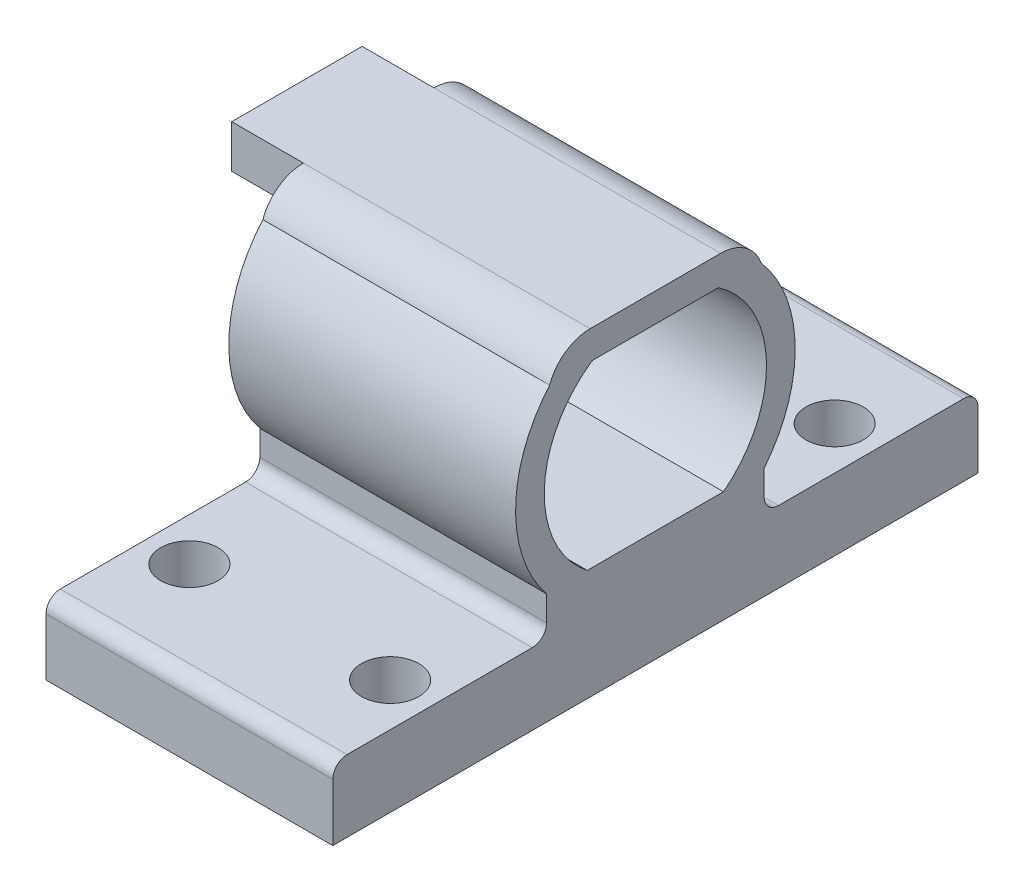
SolidWorks part; units mm, degrees
ref_plane "Front Plane" through (0, 0, 0) normal (0, 0, 1) x (1, 0, 0)
ref_plane "Top Plane" through (0, 0, 0) normal (0, 1, 0) x (1, 0, 0)
ref_plane "Right Plane" through (0, 0, 0) normal (1, 0, 0) x (0, 0, -1)
sketch "Sketch1" plane through (0, 0, 0) normal (0, 0, 1) x (1, 0, 0)
  line L1 (-5.0753, 3.8065) -> (14.9247, 3.8065)
  line L2 (-5.0753, 3.8065) -> (-5.0753, -0.9435)
  line L3 (-5.0753, -0.9435) -> (14.9247, -0.9435)
  line L4 (14.9247, 3.8065) -> (14.9247, -0.9435)
  dimension "D1" = 4.75
  dimension "D2" = 20
extrude "Boss-Extrude1" add sketch "Sketch1" along normal blind 25
sketch "Sketch2" plane through (14.9247, 0, 0) normal (1, 0, 0) x (0, 0, -1)
  line L1 (-25, 3.8065) -> (0, 3.8065) construction
  line L2 (-25, -0.9435) -> (-25, 3.8065) construction
  line L3 (-7.75, 3.8065) -> (-4.913, 3.8065)
  line L4 (-17.25, 3.8065) -> (-20.087, 3.8065)
  arc A0 (-7.75, 3.8065) -> (-17.25, 3.8065) centre (-12.5, 9.9302) ccw
  arc A1 (-4.913, 3.8065) -> (-20.087, 3.8065) centre (-12.5, 9.9302) ccw
  dimension "D1" = 7.75
  dimension "D4" = 9.75
  dimension "D2" = 9.5
  dimension "D3" = 12.5
extrude "Boss-Extrude3" add sketch "Sketch2" against normal up to surface (20 mm away) up to face at (-5.0753, 1.4315, 12.5)
sketch "Sketch5" plane through (14.9247, 0, 0) normal (1, 0, 0) x (0, 0, -1)
  line L0 (-25, -0.9435) -> (-25, 3.8065) construction
  line L1 (-20.087, 3.8065) -> (-25, 3.8065)
  line L2 (-20.087, 3.8065) -> (-20.087, 1.0565)
  line L3 (-20.087, 1.0565) -> (-25, 1.0565)
  line L4 (-25, 3.8065) -> (-25, 1.0565)
  line L5 (0, -0.9435) -> (0, 3.8065) construction
  line L6 (-4.913, 3.8065) -> (0, 3.8065)
  line L7 (-4.913, 3.8065) -> (-4.913, 1.0565)
  line L8 (-4.913, 1.0565) -> (0, 1.0565)
  line L9 (0, 3.8065) -> (0, 1.0565)
  line L10 (-25, -0.9435) -> (0, -0.9435) construction
  dimension "D1" = 2
  dimension "D2" = 2
extrude "Cut-Extrude1" cut sketch "Sketch5" against normal through all
sketch "Sketch9" plane through (14.9247, 0, 0) normal (1, 0, 0) x (0, 0, -1)
  line L0 (-17.25, 3.8065) -> (-7.75, 3.8065) construction
  line L1 (-22.33, 21.4888) -> (-1.8658, 21.4888)
  line L2 (-22.33, 21.4888) -> (-22.33, 16.3065)
  line L3 (-22.33, 16.3065) -> (-1.8658, 16.3065)
  line L4 (-1.8658, 21.4888) -> (-1.8658, 16.3065)
  dimension "D1" = 12.5
extrude "Cut-Extrude3" cut sketch "Sketch9" against normal through all
sketch "Sketch10" plane through (14.9247, 0, 0) normal (1, 0, 0) x (0, 0, -1)
  line L0 (-19.876, 16.3065) -> (-5.124, 16.3065)
  line L1 (-5.124, 16.3065) -> (-5.124, 18.3065)
  line L2 (-5.124, 18.3065) -> (-19.876, 18.3065)
  line L3 (-19.876, 18.3065) -> (-19.876, 16.3065)
  dimension "D1" = 2
extrude "Boss-Extrude4" add sketch "Sketch10" against normal up to surface (20 mm away) up to face at (-5.0753, 5.9316, 12.5)
fillet "Fillet1" radius 3 1 edges at (4.9247, 18.3065, 5.124)
fillet "Fillet2" radius 3 1 edges at (4.9247, 18.3065, 19.876)
sketch "Sketch11" plane through (0, 0, 0) normal (0, 0, -1) x (-1, 0, 0)
  line L1 (-14.9247, 1.0565) -> (5.0753, 1.0565)
  line L2 (-14.9247, 1.0565) -> (-14.9247, -0.9435)
  line L3 (-14.9247, -0.9435) -> (5.0753, -0.9435)
  line L4 (5.0753, 1.0565) -> (5.0753, -0.9435)
extrude "Boss-Extrude5" add sketch "Sketch11" along normal blind 10
sketch "Sketch12" plane through (0, 0, 25) normal (0, 0, 1) x (1, 0, 0)
  line L1 (-5.0753, 1.0565) -> (14.9247, 1.0565)
  line L2 (-5.0753, 1.0565) -> (-5.0753, -0.9435)
  line L3 (-5.0753, -0.9435) -> (14.9247, -0.9435)
  line L4 (14.9247, 1.0565) -> (14.9247, -0.9435)
extrude "Boss-Extrude6" add sketch "Sketch12" along normal blind 10
fillet "Fillet5" radius 1 1 edges at (4.9247, 1.0565, 35)
fillet "Fillet6" radius 1 1 edges at (4.9247, 1.0565, -10)
sketch "Sketch13" plane through (0, 1.0565, 0) normal (0, 1, 0) x (1, 0, 0)
  line L0 (-5.0753, -34) -> (-5.0753, -20.087) construction
  line L1 (-5.0753, -34) -> (14.9247, -34) construction
  line L2 (14.9247, 9) -> (-5.0753, 9) construction
  line L3 (14.9247, -34) -> (14.9247, -20.087) construction
  line L4 (-5.0753, -4.913) -> (-5.0753, 9) construction
  circle A0 centre (-2.0753, -28) radius 2
  circle A1 centre (11.9247, -28) radius 2
  circle A2 centre (11.9247, 3) radius 2
  circle A3 centre (-2.0753, 3) radius 2
  dimension "D1" = 4
  dimension "D2" = 3
  dimension "D3" = 6
  dimension "D6" = 6
  dimension "D7" = 6
  dimension "D8" = 3
  dimension "D9" = 3
  dimension "D4" = 2
  dimension "D5" = 2
extrude "Cut-Extrude4" cut sketch "Sketch13" against normal through all
fillet "Fillet7" radius 1 1 edges at (4.9247, 1.0565, 20.087)
fillet "Fillet8" radius 1 1 edges at (4.9247, 1.0565, 4.913)
sketch "Sketch14" plane through (-5.0753, 0, 0) normal (-1, 0, 0) x (0, 0, 1)
  line L0 (17.0476, 18.3065) -> (7.9524, 18.3065) construction
  line L1 (16.2674, 18.3065) -> (9.2674, 18.3065)
  line L2 (16.2674, 18.3065) -> (16.2674, 16.3065)
  line L3 (16.2674, 16.3065) -> (9.2674, 16.3065)
  line L4 (9.2674, 18.3065) -> (9.2674, 16.3065)
  line L5 (8.0948, 16.3065) -> (16.9052, 16.3065) construction
  dimension "D1" = 7
  dimension "D2" = 1.315
extrude "Boss-Extrude7" add sketch "Sketch14" along normal blind 5 separate body
sketch "Sketch15" plane through (0, 18.3065, 0) normal (0, -1, 0) x (1, 0, 0)
  line L1 (-10.0753, 7.9524) -> (-5.0753, 7.9524)
  line L2 (-10.0753, 7.9524) -> (-10.0753, 17.0476)
  line L3 (-10.0753, 17.0476) -> (-5.0753, 17.0476)
  line L4 (-5.0753, 7.9524) -> (-5.0753, 17.0476)
  line L6 (-5.0753, 8.0948) -> (-5.0753, 16.9052) construction
  line L7 (14.9247, 7.9524) -> (-5.0753, 7.9524) construction
  line L8 (-5.0753, 17.0476) -> (14.9247, 17.0476) construction
  dimension "D1" = 5
extrude "Boss-Extrude8" add sketch "Sketch15" along normal blind 3
sketch "Sketch16" plane through (0, -0.9435, 0) normal (0, -1, 0) x (1, 0, 0)
  line L1 (14.9247, -10) -> (-5.0753, -10)
  line L2 (14.9247, -10) -> (14.9247, 35)
  line L3 (14.9247, 35) -> (-5.0753, 35)
  line L4 (-5.0753, -10) -> (-5.0753, 35)
  circle A0 centre (11.9247, -3) radius 2
  circle A1 centre (11.9247, 28) radius 2
  circle A2 centre (-2.0753, 28) radius 2
  circle A3 centre (-2.0753, -3) radius 2
extrude "Boss-Extrude9" add sketch "Sketch16" along normal blind 3
